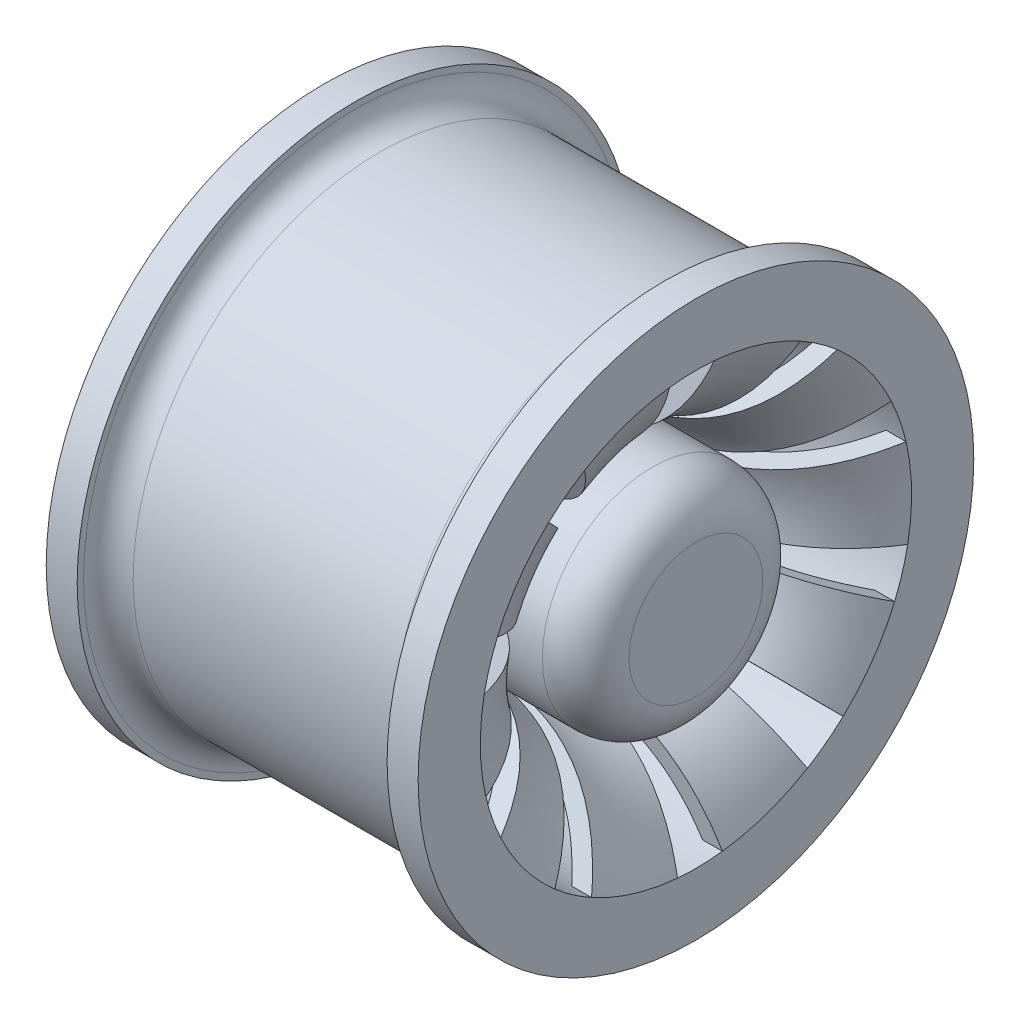
SolidWorks part; units mm, degrees
ref_plane "Front Plane" through (0, 0, 0) normal (0, 0, 1) x (1, 0, 0)
ref_plane "Top Plane" through (0, 0, 0) normal (0, 1, 0) x (1, 0, 0)
ref_plane "Right Plane" through (0, 0, 0) normal (1, 0, 0) x (0, 0, -1)
sketch "Sketch1" plane through (0, 0, 0) normal (0, 0, 1) x (1, 0, 0)
  line L0 (79.674, 0) -> (30, 0) construction
  line L1 (0, 60.173) -> (0, 5) construction
  line L2 (-30, 0) -> (26.7995, 0)
  line L3 (30, 0) -> (30, 10.0279)
  line L4 (30, 10.0279) -> (25, 10.0349)
  line L5 (25, 10.0349) -> (25, 9)
  line L6 (21, 5) -> (-21, 5)
  line L7 (0, 0) -> (0, -60.173) construction
  line L8 (-25, 10.0349) -> (-25, 9)
  line L9 (-30, 10.0279) -> (-25, 10.0349)
  line L10 (-30, 0) -> (-30, 10.0279)
  line L11 (26.7995, 0) -> (-79.674, 0) construction
  line L12 (0, -13.9724) -> (0, -16.9971)
  line L13 (0, -34.7916) -> (64.8603, -34.7916) construction
  arc A0 (25, 9) -> (21, 5) centre (21, 9) cw
  arc A1 (-25, 9) -> (-21, 5) centre (-21, 9) ccw
  spline S0 degree 2 poles (30, 0) (22.9875, -19.7667) (0, -16.9971) knots 0 0 0 1 1 1
  spline S1 degree 1 poles (27.1726, 1.003) (0.3589, -14.0186) knots 0 0 1 1 construction
  spline S2 degree 2 poles (27.1726, 1.003) (27.1273, 0.8753) (26.989, 0.4958) (26.8002, -0.0013) (25.6421, -2.8956) (22.6197, -7.5771) (17.7454, -11.8162) (11.2578, -13.9987) (4.4233, -14.5034) (0.3589, -14.0186) knots 0 0 0 0.007003 0.021008 0.035013 0.1875 0.375 0.625 0.8125 1 1 1 only from (26.7995, 0) to (0.3589, -14.0186)
  spline S3 degree 2 poles (0.3589, -14.0186) (0.1794, -13.9955) (0, -13.9724) knots 0 0 0 0.183393 0.183393 0.183393
  point P4 (0, 0)
  point P7 (0, 0)
  dimension "D1" = 4
  dimension "D3" = 44.8196
  dimension "D4" = 59.9999
  dimension "D2" = 3
revolve "Revolve1" add sketch "Sketch1" angle 360 about L13 region at (-29.3405, 5.014, 0)
sketch "Sketch2" plane through (-30, 0, 0) normal (-1, 0, 0) x (0, 0, 1)
  circle A0 centre (0, -34.7916) radius 17.7945 construction
  circle A1 centre (0, -34.7916) radius 17.7945
extrude "Boss-Extrude1" add sketch "Sketch2" against normal through all
sketch "Sketch3" plane through (-30, 0, 0) normal (-1, 0, 0) x (0, 0, 1)
  circle A0 centre (0.0778, -34.9676) radius 4
extrude "Cut-Extrude2" cut sketch "Sketch3" against normal blind 55
fillet "Fillet1" radius 7 1 edges at (30, -34.7916, 17.7945) type face fillet first side face at (30, -34.7916, 17.7945) second side face at (10.3351, -34.7916, 17.7945)
sketch "Sketch4" plane through (30, 0, 0) normal (1, 0, 0) x (0, 0, -1)
  line L0 (0.3726, -17.001) -> (2.9731, -0.1273)
  line L1 (-1.7421, -17.0826) -> (-4.2663, -0.2626)
  circle A0 centre (0, -34.7916) radius 34.7916 construction
  circle A1 centre (0, -34.7916) radius 34.7916
  circle A2 centre (0, -34.7916) radius 17.7945 construction
  circle A3 centre (0, -34.7916) radius 17.7945
  circle M2 centre (0, -34.7916) radius 34.7916
extrude "Cut-Extrude3" cut sketch "Sketch4" against normal through all both and the other way through all contours A3 L0 L1 M2 region at (30, -6.9948, 0.6635)
pattern_circular "CirPattern1" count 10 over 360 about axis through (23, -34.7916, 0) along (-1, 0, 0) of "Cut-Extrude3"
